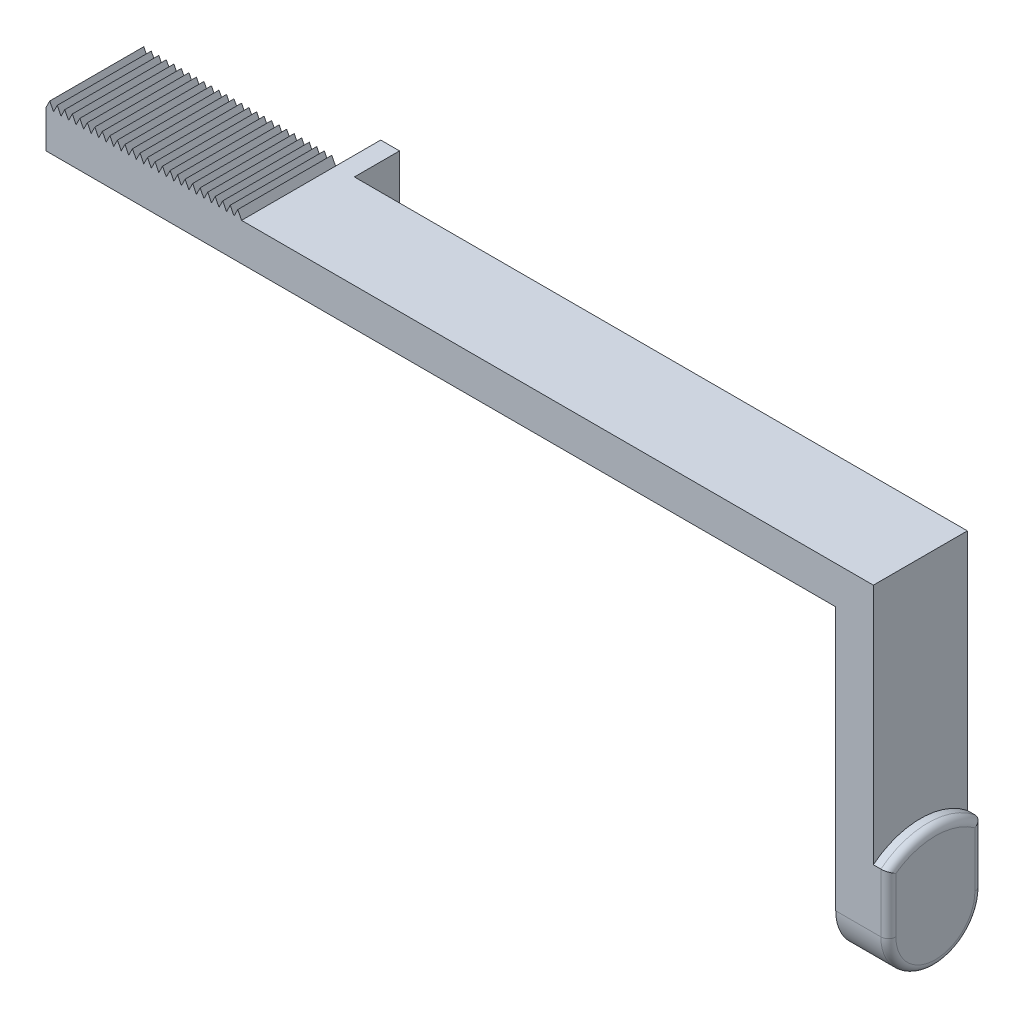
SolidWorks part; units mm, degrees
ref_plane "Plan de face" through (0, 0, 0) normal (0, 0, 1) x (1, 0, 0)
ref_plane "Plan de dessus" through (0, 0, 0) normal (0, 1, 0) x (1, 0, 0)
ref_plane "Plan de droite" through (0, 0, 0) normal (1, 0, 0) x (0, 0, -1)
sketch "Esquisse1" plane through (0, 0, 0) normal (0, 0, 1) x (1, 0, 0)
  line L1 (-214.7011, 1.8406) -> (5.2989, 1.8406)
  line L2 (-214.7011, 1.8406) -> (-214.7011, -8.1594)
  line L3 (-214.7011, -8.1594) -> (5.2989, -8.1594)
  line L4 (5.2989, 1.8406) -> (5.2989, -8.1594)
  line L5 (-214.7011, 1.8406) -> (5.2989, -8.1594) construction
  line L6 (-214.7011, -8.1594) -> (5.2989, 1.8406) construction
  line L7 (5.2989, -8.1594) -> (-4.7011, -8.1594)
  line L8 (5.2989, -8.1594) -> (5.2989, -98.1594)
  line L9 (5.2989, -98.1594) -> (-4.7011, -98.1594)
  line L10 (-4.7011, -8.1594) -> (-4.7011, -98.1594)
  point P0 (-104.7011, -3.1594)
  dimension "D1" = 220
  dimension "D2" = 10
  dimension "D3" = 10
  dimension "D4" = 90
extrude "Boss.-Extru.1" add sketch "Esquisse1" along normal blind 25 contours L4 L1 L2 L3 | L3 L10 L9 L8 region at (-104.7011, -3.1594, 0) region at (0.2989, -53.1594, 0)
ref_plane "Plan1" through (0, 0, 12.5) normal (0, 0, 1) x (1, 0, 0)
sketch "Esquisse2" plane through (0, 0, 12.5) normal (0, 0, 1) x (1, 0, 0)
  line L0 (-214.7011, 1.8406) -> (-213.7011, 3.8406)
  line L1 (-213.7011, 3.8406) -> (-212.7011, 1.8406)
  line L2 (-214.7011, 1.8406) -> (5.2989, 1.8406) construction
  line L3 (-212.7011, 1.8406) -> (-211.7011, 3.8406)
  line L4 (-211.7011, 3.8406) -> (-210.7011, 1.8406)
  line L5 (-212.7011, 1.8406) -> (-214.7011, 1.8406)
  line L6 (-210.7011, 1.8406) -> (-212.7011, 1.8406)
  line L43 (-208.7011, 1.8406) -> (-210.7011, 1.8406)
  line L48 (-210.7011, 1.8406) -> (-209.7011, 3.8406)
  line L49 (-209.7011, 3.8406) -> (-208.7011, 1.8406)
  line L50 (-208.7011, 1.8406) -> (-207.7011, 3.8406)
  line L51 (-207.7011, 3.8406) -> (-206.7011, 1.8406)
  line L52 (-206.7011, 1.8406) -> (-208.7011, 1.8406)
  line L53 (-204.7011, 1.8406) -> (-206.7011, 1.8406)
  line L54 (-206.7011, 1.8406) -> (-205.7011, 3.8406)
  line L55 (-205.7011, 3.8406) -> (-204.7011, 1.8406)
  line L56 (-204.7011, 1.8406) -> (-203.7011, 3.8406)
  line L57 (-203.7011, 3.8406) -> (-202.7011, 1.8406)
  line L58 (-202.7011, 1.8406) -> (-204.7011, 1.8406)
  line L59 (-200.7011, 1.8406) -> (-202.7011, 1.8406)
  line L60 (-202.7011, 1.8406) -> (-201.7011, 3.8406)
  line L61 (-201.7011, 3.8406) -> (-200.7011, 1.8406)
  line L62 (-200.7011, 1.8406) -> (-199.7011, 3.8406)
  line L63 (-199.7011, 3.8406) -> (-198.7011, 1.8406)
  line L64 (-198.7011, 1.8406) -> (-200.7011, 1.8406)
  line L65 (-196.7011, 1.8406) -> (-198.7011, 1.8406)
  line L66 (-198.7011, 1.8406) -> (-197.7011, 3.8406)
  line L67 (-197.7011, 3.8406) -> (-196.7011, 1.8406)
  line L68 (-196.7011, 1.8406) -> (-195.7011, 3.8406)
  line L69 (-195.7011, 3.8406) -> (-194.7011, 1.8406)
  line L70 (-194.7011, 1.8406) -> (-196.7011, 1.8406)
  line L71 (-192.7011, 1.8406) -> (-194.7011, 1.8406)
  line L72 (-194.7011, 1.8406) -> (-193.7011, 3.8406)
  line L73 (-193.7011, 3.8406) -> (-192.7011, 1.8406)
  line L74 (-192.7011, 1.8406) -> (-191.7011, 3.8406)
  line L75 (-191.7011, 3.8406) -> (-190.7011, 1.8406)
  line L76 (-190.7011, 1.8406) -> (-192.7011, 1.8406)
  line L77 (-188.7011, 1.8406) -> (-190.7011, 1.8406)
  line L78 (-190.7011, 1.8406) -> (-189.7011, 3.8406)
  line L79 (-189.7011, 3.8406) -> (-188.7011, 1.8406)
  line L80 (-188.7011, 1.8406) -> (-187.7011, 3.8406)
  line L81 (-187.7011, 3.8406) -> (-186.7011, 1.8406)
  line L82 (-186.7011, 1.8406) -> (-188.7011, 1.8406)
  line L83 (-184.7011, 1.8406) -> (-186.7011, 1.8406)
  line L84 (-186.7011, 1.8406) -> (-185.7011, 3.8406)
  line L85 (-185.7011, 3.8406) -> (-184.7011, 1.8406)
  line L86 (-184.7011, 1.8406) -> (-183.7011, 3.8406)
  line L87 (-183.7011, 3.8406) -> (-182.7011, 1.8406)
  line L88 (-182.7011, 1.8406) -> (-184.7011, 1.8406)
  line L89 (-180.7011, 1.8406) -> (-182.7011, 1.8406)
  line L90 (-182.7011, 1.8406) -> (-181.7011, 3.8406)
  line L91 (-181.7011, 3.8406) -> (-180.7011, 1.8406)
  line L92 (-180.7011, 1.8406) -> (-179.7011, 3.8406)
  line L93 (-179.7011, 3.8406) -> (-178.7011, 1.8406)
  line L94 (-178.7011, 1.8406) -> (-180.7011, 1.8406)
  line L95 (-176.7011, 1.8406) -> (-178.7011, 1.8406)
  line L96 (-178.7011, 1.8406) -> (-177.7011, 3.8406)
  line L97 (-177.7011, 3.8406) -> (-176.7011, 1.8406)
  line L98 (-176.7011, 1.8406) -> (-175.7011, 3.8406)
  line L99 (-175.7011, 3.8406) -> (-174.7011, 1.8406)
  line L100 (-174.7011, 1.8406) -> (-176.7011, 1.8406)
  line L101 (-172.7011, 1.8406) -> (-174.7011, 1.8406)
  line L102 (-174.7011, 1.8406) -> (-173.7011, 3.8406)
  line L103 (-173.7011, 3.8406) -> (-172.7011, 1.8406)
  line L104 (-172.7011, 1.8406) -> (-171.7011, 3.8406)
  line L105 (-171.7011, 3.8406) -> (-170.7011, 1.8406)
  line L106 (-170.7011, 1.8406) -> (-172.7011, 1.8406)
  line L107 (-168.7011, 1.8406) -> (-170.7011, 1.8406)
  line L108 (-170.7011, 1.8406) -> (-169.7011, 3.8406)
  line L109 (-169.7011, 3.8406) -> (-168.7011, 1.8406)
  line L110 (-168.7011, 1.8406) -> (-167.7011, 3.8406)
  line L111 (-167.7011, 3.8406) -> (-166.7011, 1.8406)
  line L112 (-166.7011, 1.8406) -> (-168.7011, 1.8406)
  line L113 (-164.7011, 1.8406) -> (-166.7011, 1.8406)
  line L114 (-166.7011, 1.8406) -> (-165.7011, 3.8406)
  line L115 (-165.7011, 3.8406) -> (-164.7011, 1.8406)
  line L116 (-164.7011, 1.8406) -> (-163.7011, 3.8406)
  line L117 (-163.7011, 3.8406) -> (-162.7011, 1.8406)
  line L118 (-162.7011, 1.8406) -> (-164.7011, 1.8406)
  dimension "D1" = 2
  dimension "D2" = 2
  dimension "D3" = 1
  dimension "D4" = 2
  dimension "D5" = 1
  dimension "D6" = 2
  dimension "D7" = 13
extrude "Boss.-Extru.2" add sketch "Esquisse2" along normal mid plane 25 contours L78 | L71 L73 L72 | L69 | L65 L67 L66 | L63 | L57 | L51 | L43 L49 L48 | L5 L1 L0 | L6 L4 L3 | L74 L75 L76 | L60 L61 L59 | L54 L55 L53 | L80 L81 L82 | L83 L84 L85 | L86 L87 L88 | L89 L90 L91 | L92 L93 L94 | L95 L96 L97 | L98 L99 L100 | L101 L102 L103 | L104 L105 L106 | L107 L108 L109 | L110 L111 L112 | L113 L114 L115 | L116 L117 L118 region at (-189.7011, 2.5073, 12.5) region at (-193.7011, 2.5073, 12.5) region at (-195.7011, 2.5073, 12.5) region at (-197.7011, 2.5073, 12.5) region at (-199.7011, 2.5073, 12.5) region at (-203.7011, 2.5073, 12.5) region at (-207.7011, 2.5073, 12.5) region at (-209.7011, 2.5073, 12.5) region at (-211.7011, 2.5073, 12.5) region at (-213.7011, 2.5073, 12.5)
sketch "Esquisse3" plane through (-4.7011, 0, 0) normal (-1, 0, 0) x (0, 0, 1)
  line L0 (12.5, -45.1) -> (12.5, 45.1) construction
  line L1 (25, -98.1594) -> (0, -98.1594) construction
  circle A0 centre (12.5, -78.1594) radius 20
  circle A1 centre (12.5, -78.1594) radius 15
  dimension "D1" = 40
  dimension "D2" = 20
  dimension "D3" = 30
extrude "Boss.-Extru.3" add sketch "Esquisse3" against normal blind 10
sketch "Esquisse4" plane through (-4.7011, 0, 0) normal (-1, 0, 0) x (0, 0, 1)
  circle A0 centre (12.5, -78.1594) radius 20
  circle A1 centre (12.5, -78.1594) radius 15
  circle A2 centre (12.5, -78.1594) radius 24.6712
  line M5 (0, -93.7719) -> (0, -98.1594)
  line M6 (0, -98.1594) -> (25, -98.1594)
  line M7 (25, -98.1594) -> (25, -93.7719)
  line M11 (0, -69.8678) -> (0, -86.451)
  line M14 (25, -86.451) -> (25, -69.8678)
extrude "Enlèv. mat.-Extru.1" cut sketch "Esquisse4" against normal through all contours A1 M14 M11 | A0 M6 M7 | A0 M5 M6 region at (-4.7011, -96.8722, 3.0523) region at (-4.7011, -96.8722, 21.9477) region at (-4.7011, -78.1594, 12.5)
sketch "Esquisse5" plane through (-214.7011, 0, 0) normal (-1, 0, 0) x (0, 0, 1)
  line L0 (25, -8.1594) -> (0, -8.1594) construction
  line L1 (7.5, -8.1594) -> (17.5, -8.1594)
  line L2 (7.5, -8.1594) -> (7.5, -3.1594)
  line L3 (7.5, -3.1594) -> (17.5, -3.1594)
  line L4 (17.5, -8.1594) -> (17.5, -3.1594)
  line L5 (0, 1.8406) -> (0, -8.1594) construction
  dimension "D1" = 7.5
  dimension "D2" = 10
  dimension "D3" = 5
extrude "Enlèv. mat.-Extru.2" cut sketch "Esquisse5" against normal blind 190
sketch "Esquisse6" plane through (5.2989, 0, 0) normal (1, 0, 0) x (0, 0, -1)
  circle A0 centre (-12.5, -78.1594) radius 20
extrude "Boss.-Extru.4" add sketch "Esquisse6" along normal blind 4
sketch "Esquisse8" plane through (-214.7011, 0, 0) normal (-1, 0, 0) x (0, 0, 1)
  line L0 (12.5, 1.8406) -> (12.5, -3.1594) construction
  line L1 (25, 1.8406) -> (0, 1.8406) construction
  line L2 (17.5, -3.1594) -> (7.5, -3.1594) construction
  circle A0 centre (12.5, -0.6594) radius 2
  dimension "D1" = 4
extrude "Enlèv. mat.-Extru.4" cut sketch "Esquisse8" against normal blind 6
sketch "Esquisse9" plane through (5.2989, 0, 0) normal (-1, 0, 0) x (0, 0, 1)
  point P0 (12.5, -78.1594)
sketch "Esquisse10" plane through (0, 0, 25) normal (0, 0, 1) x (1, 0, 0)
  line L0 (-214.7011, -8.1594) -> (-4.7011, -8.1594) construction
  line L3 (-162.7011, -8.1594) -> (-157.7011, -8.1594)
  line L4 (-157.7011, 1.8406) -> (-157.7011, -8.1594)
  line L5 (-162.7011, -8.1594) -> (-162.7011, 1.8406)
  line L6 (-162.7011, 1.8406) -> (-157.7011, 1.8406)
  dimension "D1" = 5
extrude "Boss.-Extru.5" add sketch "Esquisse10" along normal blind 10
sketch "Esquisse11" plane through (0, 0, 0) normal (0, 0, -1) x (-1, 0, 0)
  line L0 (157.7011, -8.1594) -> (157.7011, -13.1594)
  line L1 (162.7011, 1.8406) -> (157.7011, 1.8406)
  line L2 (162.7011, 1.8406) -> (162.7011, -8.1594)
  line L4 (157.7011, 1.8406) -> (157.7011, -8.1594)
  line L5 (157.7011, -13.1594) -> (162.7011, -13.1594)
  line L6 (162.7011, -13.1594) -> (162.7011, -8.1594)
  dimension "D1" = 5
  dimension "D2" = 5
extrude "Boss.-Extru.6" add sketch "Esquisse11" along normal blind 12
sketch "Esquisse12" plane through (5.2989, 0, 0) normal (-1, 0, 0) x (0, 0, 1)
  circle A0 centre (12.5, -78.1594) radius 15
  circle A1 centre (12.5, -78.1594) radius 10
  dimension "D1" = 20
extrude "Boss.-Extru.8" add sketch "Esquisse12" along normal blind 10
sketch "Esquisse13" plane through (-4.7011, 0, 0) normal (-1, 0, 0) x (0, 0, 1)
  line L0 (0, -62.5469) -> (0, -78.1594)
  line L1 (0, -78.1594) -> (25, -78.1594)
  line L2 (25, -78.1594) -> (25, -62.5469)
  circle A1 centre (12.5, -78.1594) radius 12.5
  circle A2 centre (12.5, -78.1594) radius 20
  arc M2 (0, -62.5469) -> (25, -62.5469) centre (12.5, -78.1594) ccw
extrude "Enlèv. mat.-Extru.5" cut sketch "Esquisse13" against normal blind 20 contours A1 L0 L2 M2 region at (-4.7011, -70.3531, -0.5356)
fillet "Congé1" radius 2 4 edges at (9.2989, -70.3531, 0) (9.2989, -90.6594, 12.5) (9.2989, -70.3531, 25) (9.2989, -58.1594, 12.5)
sketch "Esquisse14" plane through (5.2989, 0, 0) normal (-1, 0, 0) x (0, 0, 1)
  circle A0 centre (12.5, -78.1594) radius 10
extrude "Boss.-Extru.9" add sketch "Esquisse14" along normal blind 3
sketch "Esquisse15" plane through (0, 0, 35) normal (0, 0, 1) x (1, 0, 0)
  line L0 (-162.7011, 1.8406) -> (-162.7011, -8.1594)
  line L1 (-162.7011, 1.8406) -> (-157.6684, 1.8406)
  line L2 (-162.7011, -8.1594) -> (-157.6684, -8.1594)
  line L3 (-157.6684, 1.8406) -> (-157.6684, -8.1594)
extrude "Enlèv. mat.-Extru.6" cut sketch "Esquisse15" against normal up to surface (10 mm away) up to face at (-188.7011, 2.4224, 25)
